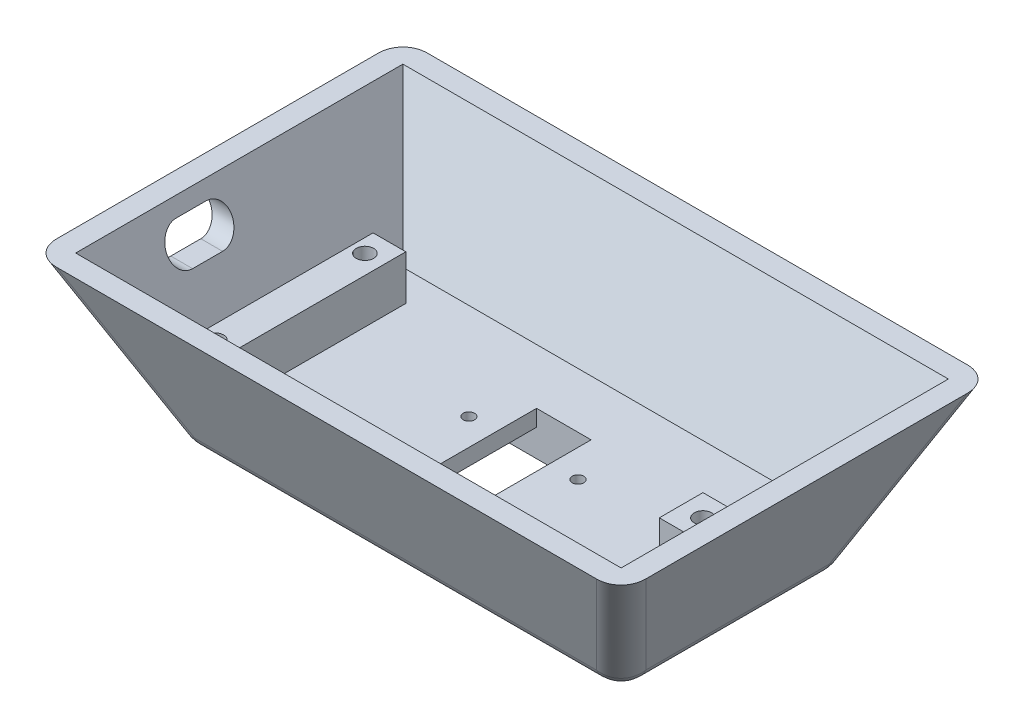
SolidWorks part; units mm, degrees
ref_plane "Front Plane" through (0, 0, 0) normal (0, 0, 1) x (1, 0, 0)
ref_plane "Top Plane" through (0, 0, 0) normal (0, 1, 0) x (1, 0, 0)
ref_plane "Right Plane" through (0, 0, 0) normal (1, 0, 0) x (0, 0, -1)
sketch "Sketch1" plane through (0, 0, 0) normal (0, 1, 0) x (1, 0, 0)
  line L1 (-40, 20) -> (40, 20)
  line L2 (-40, 20) -> (-40, -20)
  line L3 (-40, -20) -> (40, -20)
  line L4 (40, 20) -> (40, -20)
  line L5 (-40, 20) -> (40, -20) construction
  line L6 (-40, -20) -> (40, 20) construction
  point P0 (0, 0)
  dimension "D1" = 40
  dimension "D2" = 80
extrude "Base Extrusion" add sketch "Sketch1" along normal blind 30 draft 25 draft outward yes
sketch "Sketch2" plane through (0, 0, 0) normal (0, -1, 0) x (1, 0, 0)
  line L0 (0, 9.6) -> (0, 20) construction
  line L1 (-15.1, 9.6) -> (15.1, 9.6)
  line L2 (-15.1, 9.6) -> (-15.1, -9.6)
  line L3 (-15.1, -9.6) -> (15.1, -9.6)
  line L4 (15.1, 9.6) -> (15.1, -9.6)
  line L5 (-15.1, 9.6) -> (15.1, -9.6) construction
  line L6 (-15.1, -9.6) -> (15.1, 9.6) construction
  line L7 (-40, 20) -> (40, 20) construction
  point P0 (0, 0)
  dimension "D1" = 19.2
  dimension "D2" = 30.2
  dimension "D3" = 10.4
extrude "Triangle Attach Cutout" cut sketch "Sketch2" against normal blind 5
sketch "Sketch3" plane through (0, 30, 0) normal (0, 1, 0) x (1, 0, 0)
  line L17 (-49.9892, 29.9892) -> (-49.9892, -29.9892)
  line L18 (-49.9892, -29.9892) -> (49.9892, -29.9892)
  line L19 (49.9892, -29.9892) -> (49.9892, 29.9892)
  line L20 (49.9892, 29.9892) -> (-49.9892, 29.9892)
  line L21 (-49.9892, 29.9892) -> (-49.9892, -29.9892)
  line L22 (-49.9892, -29.9892) -> (49.9892, -29.9892)
  line L23 (49.9892, -29.9892) -> (49.9892, 29.9892)
  line L24 (49.9892, 29.9892) -> (-49.9892, 29.9892)
  dimension "D2" = 4
extrude "Shell out the base" cut sketch "Sketch3" against normal blind 22 draft 25
sketch "Sketch5" plane through (0, 5, 0) normal (0, -1, 0) x (1, 0, 0)
  line L0 (0, -2.1) -> (-10, -2.1) construction
  line L1 (0, -1000) -> (0, 49000) construction
  line L2 (-5.1, 5.6) -> (-5.1, 9.6) construction
  line L3 (15.1, 9.6) -> (-15.1, 9.6) construction
  line L4 (-5.1, 9.6) -> (4.9, 9.6) construction
  line L6 (4.9, 9.6) -> (-5.1, 9.6)
  line L7 (4.9, 9.6) -> (4.9, -9.6)
  line L8 (4.9, -9.6) -> (-5.1, -9.6)
  line L9 (-5.1, 9.6) -> (-5.1, -9.6)
  line L11 (-15.1, -9.6) -> (15.1, -9.6) construction
  circle A0 centre (-10, -2.1) radius 1.05
  circle A2 centre (10, -2.1) radius 1.05
  dimension "D3" = 2.1
  dimension "D1" = 10
  dimension "D2" = 2.1
  dimension "D5" = 4
  dimension "D6" = 10
extrude "LED Strip Cutout" cut sketch "Sketch5" against normal up to next
sketch "Sketch13" plane through (0, 0, 0) normal (0, 1, 0) x (1, 0, 0)
  line L0 (-39.7305, -19.7305) -> (39.7305, -19.7305) construction
  line L1 (-39.7305, -19.7305) -> (-33.7305, -19.7305)
  line L2 (-39.7305, -19.7305) -> (-39.7305, 14.2695)
  line L3 (-39.7305, 14.2695) -> (-33.7305, 14.2695)
  line L4 (-33.7305, -19.7305) -> (-33.7305, 14.2695)
  line L5 (31.7305, -4.7305) -> (39.7305, -4.7305)
  line L6 (31.7305, -4.7305) -> (31.7305, 3.2695)
  line L7 (31.7305, 3.2695) -> (39.7305, 3.2695)
  line L8 (39.7305, -4.7305) -> (39.7305, 3.2695)
  line L9 (39.7305, -19.7305) -> (39.7305, 19.7305) construction
  line L10 (31.7305, -0.7305) -> (39.7305, -0.7305) construction
  line L11 (-39.7305, 19.7305) -> (-39.7305, -19.7305) construction
  circle A0 centre (35.7305, -0.7305) radius 1.6002
  circle A1 centre (-37.2305, 10.2695) radius 1.6002
  circle A2 centre (-37.2305, -17.2305) radius 1.6002
  dimension "D6" = 2.5
  dimension "D7" = 3.2004
  dimension "D1" = 34
  dimension "D2" = 6
  dimension "D3" = 15
  dimension "D4" = 8
  dimension "D5" = 8
  dimension "D8" = 2.5
  dimension "D9" = 30
  dimension "D10" = 2.5
extrude "PCB Ledge" add sketch "Sketch13" along normal blind 8.2 from surface starting at face at (-10, 8, -1.05)
sketch "Sketch14" plane through (0, 0, 0) normal (1, 0, 0) x (0, 0, -1)
  line L0 (-12.75, 24.25) -> (-7.25, 24.25) construction
  line L1 (-12.75, 27.5) -> (-7.25, 27.5)
  line L2 (-12.75, 21) -> (-7.25, 21)
  arc A0 (-12.75, 27.5) -> (-12.75, 21) centre (-12.75, 24.25) ccw
  arc A1 (-7.25, 21) -> (-7.25, 27.5) centre (-7.25, 24.25) ccw
  point P2 (-10, 24.25)
  point P7 (-16, 24.25)
  point P8 (-4, 24.25)
  dimension "D1" = 24.25
  dimension "D4" = 12
  dimension "D2" = 10
  dimension "D3" = 6.5
extrude "USB-C Cutout" cut sketch "Sketch14" against normal up to next
fillet "Fillet1" radius 5 8 edges at (-40, 0, 0) (0, 0, 20) (40, 0, 0) (0, 0, -20) (-46.9946, 15, 26.9946) (46.9946, 15, 26.9946) (46.9946, 15, -26.9946) (-46.9946, 15, -26.9946)
